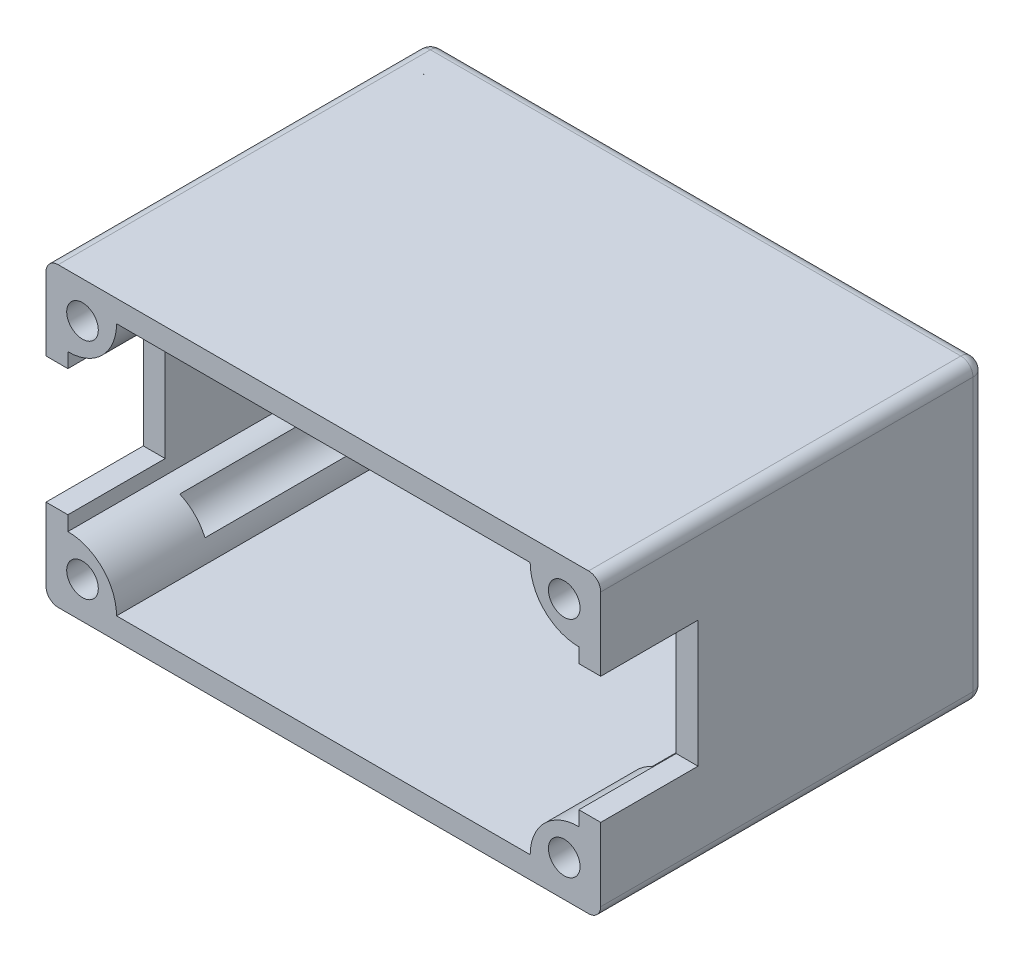
SolidWorks part; units mm, degrees
ref_plane "前视基准面" through (0, 0, 0) normal (0, 0, 1) x (1, 0, 0)
ref_plane "上视基准面" through (0, 0, 0) normal (0, 1, 0) x (1, 0, 0)
ref_plane "右视基准面" through (0, 0, 0) normal (1, 0, 0) x (0, 0, -1)
sketch "草图1" plane through (0, 0, 0) normal (0, 0, 1) x (1, 0, 0)
  line L1 (-11.4, 6.1) -> (11.4, 6.1)
  line L2 (-11.4, 6.1) -> (-11.4, -6.1)
  line L3 (-11.4, -6.1) -> (11.4, -6.1)
  line L4 (11.4, 6.1) -> (11.4, -6.1)
  line L5 (-11.4, 6.1) -> (11.4, -6.1) construction
  line L6 (-11.4, -6.1) -> (11.4, 6.1) construction
  point P0 (0, 0)
  dimension "D1" = 22.8
  dimension "D2" = 12.2
extrude "凸台-拉伸1" add sketch "草图1" along normal blind 15.8
sketch "草图2" plane through (0, 0, 15.8) normal (0, 0, 1) x (1, 0, 0)
  line L0 (11.4, 6.1) -> (-11.4, 6.1) construction
  line L1 (-10.5, 5.2) -> (10.5, 5.2)
  line L2 (-10.5, 5.2) -> (-10.5, -5.2)
  line L3 (-10.5, -5.2) -> (10.5, -5.2)
  line L4 (10.5, 5.2) -> (10.5, -5.2)
  line L5 (-11.4, 6.1) -> (-11.4, -6.1) construction
  line L6 (-11.4, -6.1) -> (11.4, -6.1) construction
  line L7 (11.4, -6.1) -> (11.4, 6.1) construction
  dimension "D1" = 0.9
  dimension "D2" = 0.9
  dimension "D3" = 0.9
  dimension "D4" = 0.9
extrude "切除-拉伸1" cut sketch "草图2" against normal blind 13.8
sketch "草图3" plane through (0, 0, 2) normal (0, 0, 1) x (1, 0, 0)
  line L0 (10.5, -5.2) -> (10.5, 5.2) construction
  line L1 (10.5, 5.2) -> (-10.5, 5.2) construction
  line L2 (10.5, -5.2) -> (10.5, 5.2) construction
  line L3 (-10.5, -5.2) -> (10.5, -5.2) construction
  line L4 (-10.5, 5.2) -> (-10.5, -5.2) construction
  circle A0 centre (9.9, 4.6) radius 0.65
  circle A1 centre (-9.9, -4.6) radius 0.65
  circle A2 centre (9.9, -4.6) radius 0.65
  circle A3 centre (-9.9, 4.6) radius 0.65
  dimension "D1" = 1.3
  dimension "D5" = 1.3
  dimension "D7" = 1.3
  dimension "D10" = 0.6
  dimension "D11" = 1.3
  dimension "D2" = 0.6
  dimension "D3" = 0.6
  dimension "D4" = 19.8
  dimension "D6" = 0.6
  dimension "D8" = 0.6
  dimension "D9" = 0.6
  dimension "D12" = 0.6
sketch "草图4" plane through (0, 0, 15.8) normal (0, 0, 1) x (1, 0, 0)
  line L0 (-11.4, 6.1) -> (-11.4, -6.1) construction
  line L1 (-11.4, 2.6) -> (-10.5, 2.6)
  line L2 (-11.4, 2.6) -> (-11.4, -2.6)
  line L3 (-11.4, -2.6) -> (-10.5, -2.6)
  line L4 (-10.5, 2.6) -> (-10.5, -2.6)
  line L5 (-10.5, 5.2) -> (-10.5, -5.2) construction
  line L6 (11.4, 6.1) -> (-11.4, 6.1) construction
  line L8 (-11.4, -6.1) -> (11.4, -6.1) construction
  dimension "D1" = 3.5
  dimension "D2" = 3.5
extrude "切除-拉伸2" cut sketch "草图4" against normal blind 4
sketch "草图7" plane through (0, 0, 2) normal (0, 0, 1) x (1, 0, 0)
  line L0 (-5.85, -2.45) -> (5.15, -2.45) construction
  line L1 (-5.85, -0.2) -> (5.15, -0.2)
  line L2 (-5.85, -4.7) -> (5.15, -4.7)
  line L3 (-10.5, -5.2) -> (10.5, -5.2) construction
  line L5 (10.5, -5.2) -> (10.5, 5.2) construction
  arc A0 (-5.85, -0.2) -> (-5.85, -4.7) centre (-5.85, -2.45) ccw
  arc A1 (5.15, -4.7) -> (5.15, -0.2) centre (5.15, -2.45) ccw
  point P2 (-0.35, -2.45)
  point P7 (-8.1, -2.45)
  point P8 (7.4, -2.45)
  dimension "D2" = 15.5
  dimension "D1" = 11
  dimension "D3" = 0.5
  dimension "D4" = 10.85
extrude "切除-拉伸5" cut sketch "草图7" against normal blind 2
fillet "圆角2" radius 0.5 4 edges at (11.4, 6.1, 7.9) (11.4, -6.1, 7.9) (-11.4, -6.1, 7.9) (-11.4, 6.1, 7.9)
sketch "草图8" plane through (0, 0, 15.8) normal (0, 0, 1) x (1, 0, 0)
  line L0 (10.5, -5.2) -> (10.5, 5.2) construction
  line L1 (10.5, 2.6) -> (11.4, 2.6)
  line L2 (10.5, 2.6) -> (10.5, -2.6)
  line L3 (10.5, -2.6) -> (11.4, -2.6)
  line L4 (11.4, 2.6) -> (11.4, -2.6)
  line L5 (11.4, -5.6) -> (11.4, 5.6) construction
  line L6 (10.9, 6.1) -> (-10.9, 6.1) construction
  line L7 (-10.9, -6.1) -> (10.9, -6.1) construction
  dimension "D1" = 3.5
  dimension "D2" = 3.5
extrude "切除-拉伸6" cut sketch "草图8" against normal blind 4
sketch "草图10" plane through (0, 0, 2) normal (0, 0, 1) x (1, 0, 0)
  line L0 (-10.5, -2.6) -> (-10.5, -5.2) construction
  line L1 (-10.5, -5.2) -> (10.5, -5.2) construction
  line L2 (-10.5, 5.2) -> (-10.5, -5.2) construction
  line L3 (-10.5, -5.2) -> (10.5, -5.2) construction
  line L4 (10.5, 5.2) -> (-10.5, 5.2) construction
  line L5 (10.5, -5.2) -> (10.5, 5.2) construction
  line L6 (10.5, -5.2) -> (10.5, -2.6) construction
  line L7 (10.5, 5.2) -> (-10.5, 5.2) construction
  line L8 (-10.5, 5.2) -> (-10.5, 2.6) construction
  line L9 (-10.5, 3.2) -> (-10.5, 5.2)
  line L10 (10.5, 2.6) -> (10.5, 5.2) construction
  line L11 (8.5, 5.2) -> (10.5, 5.2)
  line L12 (10.5, 5.2) -> (10.5, 3.2)
  line L13 (-10.5, 5.2) -> (-8.5, 5.2)
  line L14 (10.5, -3.2) -> (10.5, -5.2)
  line L15 (10.5, -5.2) -> (8.5, -5.2)
  line L16 (-10.5, -3.2) -> (-10.5, -5.2)
  line L17 (-10.5, -5.2) -> (-8.5, -5.2)
  arc A0 (-10.5, -3.2) -> (-8.5, -5.2) centre (-10.5, -5.2) cw
  arc A1 (10.5, -3.2) -> (8.5, -5.2) centre (10.5, -5.2) ccw
  arc A2 (-8.5, 5.2) -> (-10.5, 3.2) centre (-10.5, 5.2) cw
  arc A3 (8.5, 5.2) -> (10.5, 3.2) centre (10.5, 5.2) ccw
  dimension "D3" = 2
  dimension "D6" = 2
  dimension "D7" = 2
  dimension "D9" = 2
  dimension "D10" = 2
  dimension "D12" = 2
  dimension "D1" = 2
  dimension "D2" = 2
  dimension "D4" = 2
  dimension "D5" = 2
  dimension "D8" = 2
  dimension "D11" = 2
extrude "凸台-拉伸2" add sketch "草图10" along normal blind 13.8
extrude "切除-拉伸8" cut sketch "草图3" along normal through all and the other way through all
sketch "草图9" plane through (0, 0, 0) normal (0, 0, -1) x (-1, 0, 0)
  circle A0 centre (-9.9, 4.6) radius 1.25
  circle A1 centre (9.9, 4.6) radius 1.25
  circle A3 centre (-9.9, -4.6) radius 1.25
  circle A4 centre (9.9, -4.6) radius 1.25
  dimension "D1" = 2.5
  dimension "D2" = 2.5
  dimension "D3" = 2.5
  dimension "D4" = 2.5
extrude "切除-拉伸9" cut sketch "草图9" against normal blind 12
fillet "圆角3" radius 0.5 8 edges at (-11.2536, 5.9536, 0) (-11.4, 0, 0) (-11.2536, -5.9536, 0) (0, -6.1, 0) (11.2536, -5.9536, 0) (11.2536, 5.9536, 0) (11.4, 0, 0) (0, 6.1, 0)
